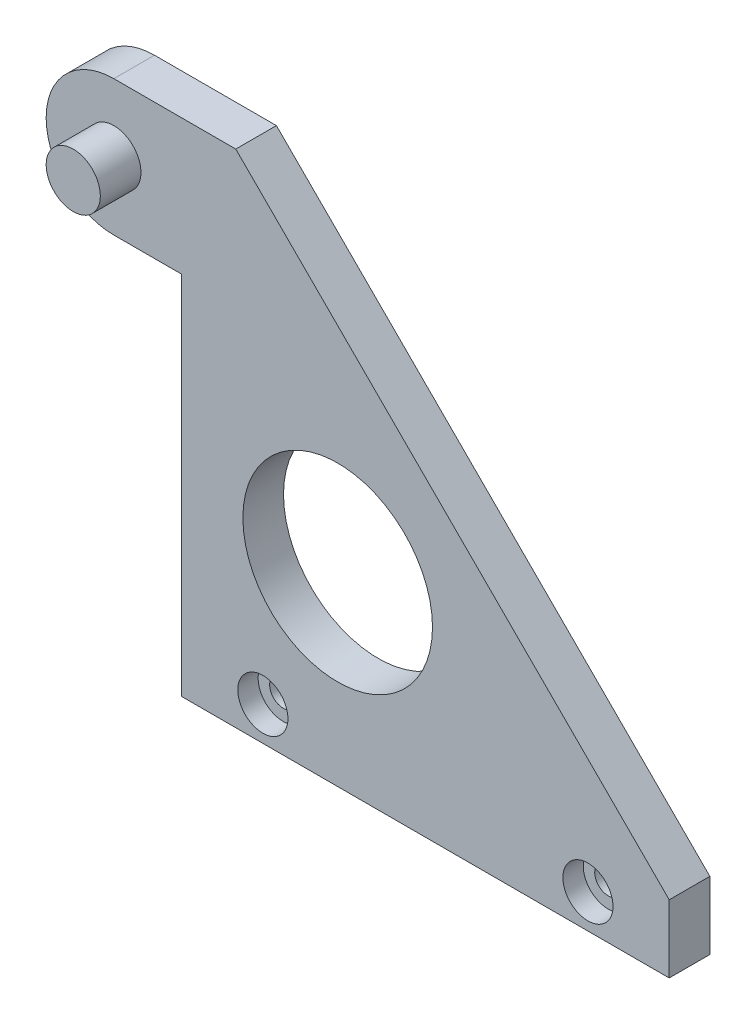
SolidWorks part; units mm, degrees
ref_plane "前视基准面" through (0, 0, 0) normal (0, 0, 1) x (1, 0, 0)
ref_plane "上视基准面" through (0, 0, 0) normal (0, 1, 0) x (1, 0, 0)
ref_plane "右视基准面" through (0, 0, 0) normal (1, 0, 0) x (0, 0, -1)
sketch "草图1" plane through (0, 0, 0) normal (0, 0, 1) x (1, 0, 0)
  line L0 (-18, 0) -> (18, 0)
  line L1 (18, 0) -> (18, 5)
  line L2 (18, 5) -> (-14, 37)
  line L3 (-14, 37) -> (-28, 37)
  line L4 (-28, 37) -> (-28, 27)
  line L5 (-28, 27) -> (-18, 27)
  line L6 (-18, 27) -> (-18, 0)
  point P3 (-28, 32)
  point P4 (0, 0)
  dimension "D1" = 36
  dimension "D2" = 5
  dimension "D3" = 10
  dimension "D4" = 27
  dimension "D5" = 135
extrude "凸台-拉伸1" add sketch "草图1" along normal blind 3
sketch "草图3" plane through (0, 0, 3) normal (0, 0, 1) x (1, 0, 0)
  circle A0 centre (-6.4764, 13.6875) radius 7
  dimension "D1" = 14
extrude "切除-拉伸1" cut sketch "草图3" against normal through all
sketch "草图4" plane through (0, 0, 3) normal (0, 0, 1) x (1, 0, 0)
  line L0 (-18, 5) -> (18, 0) construction
  line L1 (-18, 0) -> (18, 0) construction
  line L2 (-18, 0) -> (-18, 5) construction
  line L3 (-18, 5) -> (18, 5) construction
  line L4 (18, 0) -> (18, 5) construction
  line L5 (18, 5) -> (-18, 0) construction
  line L6 (-1000, 2.5) -> (49000, 2.5) construction
  line L7 (0, -997.5) -> (0, 49002.5) construction
  circle A0 centre (12, 2.5) radius 1
  circle A1 centre (-12, 2.5) radius 1
  point P9 (0, 2.5)
  dimension "D1" = 2
  dimension "D2" = 12
extrude "切除-拉伸2" cut sketch "草图4" against normal through all
sketch "草图5" plane through (0, 0, 3) normal (0, 0, 1) x (1, 0, 0)
  line L0 (-28, 37) -> (-18, 27) construction
  line L1 (-28, 37) -> (-18, 37) construction
  line L2 (-28, 37) -> (-28, 27) construction
  line L3 (-28, 27) -> (-18, 27) construction
  line L4 (-18, 37) -> (-18, 27) construction
  line L5 (-28, 27) -> (-18, 37) construction
  circle A0 centre (-23, 32) radius 2
  dimension "D1" = 4
extrude "凸台-拉伸2" add sketch "草图5" along normal blind 3
fillet "圆角1" 2 edges at (-28, 37, 1.5) (-28, 27, 1.5) type full round first side face at (-21, 37, 1.5) second side face at (-23, 27, 1.5) middle face at (-28, 32, 1.5)
sketch "草图6" plane through (0, 0, 3) normal (0, 0, 1) x (1, 0, 0)
  circle A0 centre (12, 2.5) radius 1.85
  circle A1 centre (-12, 2.5) radius 1.85
  dimension "D1" = 3.7
extrude "切除-拉伸3" cut sketch "草图6" against normal blind 1.5
